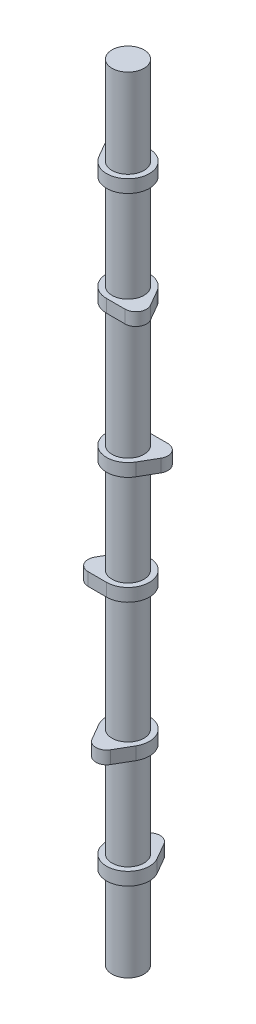
SolidWorks part; units mm, degrees
ref_plane "Front Plane" through (0, 0, 0) normal (0, 0, 1) x (1, 0, 0)
ref_plane "Top Plane" through (0, 0, 0) normal (0, 1, 0) x (1, 0, 0)
ref_plane "Right Plane" through (0, 0, 0) normal (1, 0, 0) x (0, 0, -1)
sketch "Sketch1" plane through (0, 0, 0) normal (0, 1, 0) x (1, 0, 0)
  line L0 (-5.4993, 15.875) -> (-10.9985, 6.35)
  line L1 (5.4993, 15.875) -> (10.9985, 6.35)
  arc A0 (-10.9985, 6.35) -> (10.9985, 6.35) centre (0, 0) ccw
  arc A1 (5.4993, 15.875) -> (-5.4993, 15.875) centre (0, 12.7) ccw
  dimension "D1" = 12.7
  dimension "D2" = 25.4
  dimension "D3" = 12.7
extrude "Boss-Extrude1" add sketch "Sketch1" along normal blind 7.62
ref_axis "Axis1" through (0, 51.189, 0) along (0, -1, 0)
pattern_linear "LPattern4" count 2 spacing 64.25 along (0, 1, 0) of bodies 101
move or copy body "Body-Move/Copy6" bodies to move or copy 104 copy no rotation origin (0, 0, 0) rotation axis (0, 1, 0) rotation angle 180
pattern_linear "LPattern7" count 3 spacing 146.05 along (0, 1, 0) of bodies 101 121
move or copy body "Body-Move/Copy7" bodies to move or copy 122 124 copy no rotation origin (0, 0, 0) rotation axis (0, 1, 0) rotation angle 120
move or copy body "Body-Move/Copy8" bodies to move or copy 123 125 copy no rotation origin (0, 0, 0) rotation axis (0, -1, 0) rotation angle 120
sketch "Sketch2" plane through (0, 0, 0) normal (0, 1, 0) x (1, 0, 0)
  circle A0 centre (0, 0) radius 9.5
  dimension "D1" = 19
extrude "Boss-Extrude2" add sketch "Sketch2" along normal blind 466.09 from offset 49.53 offset against normal yes
equation "\"`12.70\"=38.3828"
